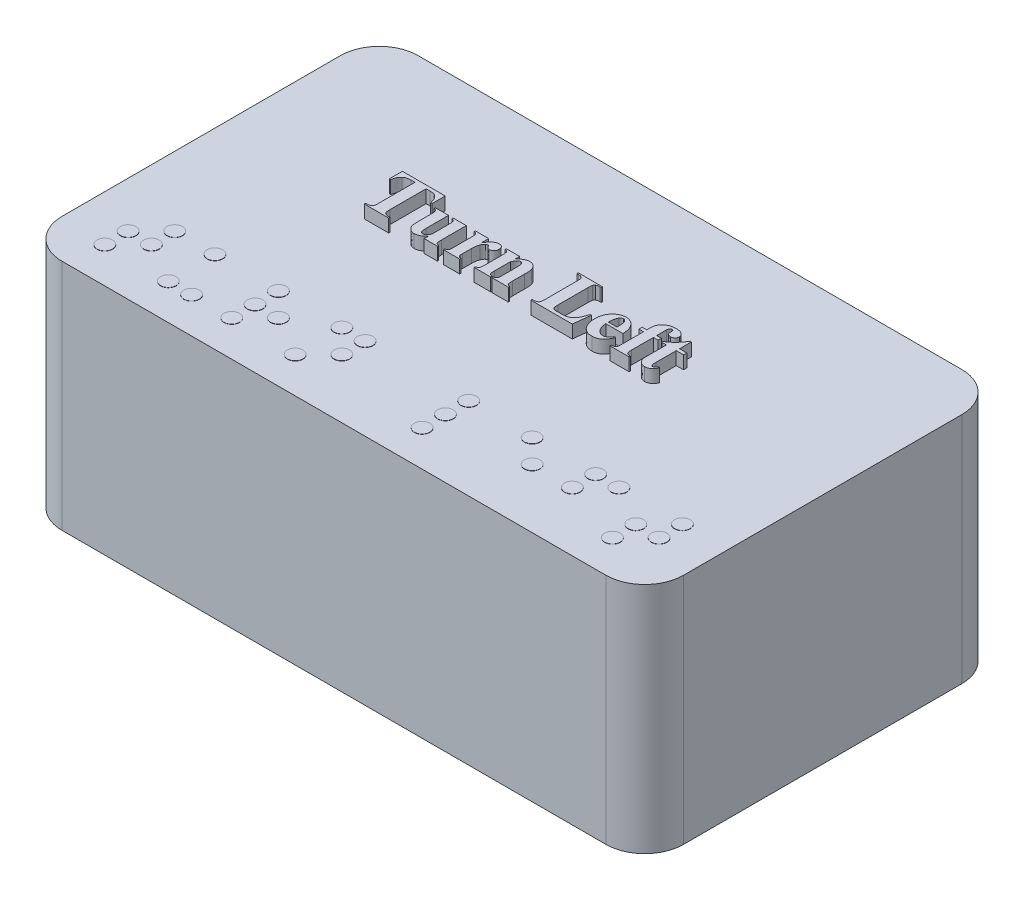
SolidWorks part; units mm, degrees
ref_plane "Front Plane" through (0, 0, 0) normal (0, 0, 1) x (1, 0, 0)
ref_plane "Top Plane" through (0, 0, 0) normal (0, 1, 0) x (1, 0, 0)
ref_plane "Right Plane" through (0, 0, 0) normal (1, 0, 0) x (0, 0, -1)
sketch "Sketch1" plane through (0, 0, 0) normal (0, 1, 0) x (1, 0, 0)
  line L1 (-30.48, 17.4625) -> (30.48, 17.4625)
  line L2 (-30.48, 17.4625) -> (-30.48, -17.4625)
  line L3 (-30.48, -17.4625) -> (30.48, -17.4625)
  line L4 (30.48, 17.4625) -> (30.48, -17.4625)
  line L5 (-30.48, 17.4625) -> (30.48, -17.4625) construction
  line L6 (-30.48, -17.4625) -> (30.48, 17.4625) construction
  point P0 (0, 0)
  dimension "D1" = 60.96
  dimension "D2" = 34.925
extrude "Boss-Extrude1" add sketch "Sketch1" along normal blind 22.86
sketch "Sketch2" plane through (0, 22.86, 0) normal (0, 1, 0) x (1, 0, 0)
  line L0 (-30.48, 17.4625) -> (-30.48, 0.9525) construction
  line L1 (-30.48, 17.4625) -> (-30.48, -17.4625) construction
  line L2 (-30.48, 0.9525) -> (30.48, 0.9525) construction
  line L3 (30.48, -17.4625) -> (30.48, 17.4625) construction
  line L4 (-30.48, 0.9525) -> (-30.48, -9.525) construction
  text T0 "<b>        Turn Left</b>" font "Times New Roman" height in points 19
  dimension "D1" = 16.51
sketch "Sketch3" plane through (0, 22.86, 0) normal (0, 1, 0) x (1, 0, 0)
  line L0 (-30.48, 17.4625) -> (-30.48, 0.9525) construction
  line L1 (-30.48, 17.4625) -> (-30.48, -17.4625) construction
  line L2 (-7.295, -11.6811) -> (-7.295, -13.9671) construction
  line L3 (-25.964, -9.3951) -> (-23.678, -9.3951) construction
  line L4 (-25.964, -9.3951) -> (-25.964, -11.6811) construction
  line L5 (-23.678, -9.3951) -> (-23.678, -11.6811) construction
  line L6 (-25.964, -9.3951) -> (-19.741, -9.3951) construction
  line L7 (-19.741, -9.3951) -> (-17.455, -9.3951) construction
  line L8 (-17.455, -9.3951) -> (-17.455, -11.6811) construction
  line L9 (-19.741, -9.3951) -> (-19.741, -11.6811) construction
  line L10 (-19.741, -11.6811) -> (-19.741, -13.9671) construction
  line L11 (-19.741, -9.3951) -> (-13.518, -9.3951) construction
  line L12 (-13.518, -9.3951) -> (-7.295, -9.3951) construction
  line L13 (-7.295, -9.3951) -> (-7.295, -11.6811) construction
  line L14 (-7.295, -9.3951) -> (-5.009, -9.3951) construction
  line L15 (-7.295, -9.3951) -> (-1.072, -9.3951) construction
  line L16 (-1.072, -9.3951) -> (-1.072, -13.9671) construction
  line L17 (-1.072, -11.6811) -> (1.214, -11.6811) construction
  line L18 (-1.072, -9.3951) -> (5.151, -9.3951) construction
  line L19 (5.151, -9.3951) -> (5.151, -11.6811) construction
  line L20 (5.151, -11.6811) -> (5.151, -13.9671) construction
  line L21 (5.151, -11.6811) -> (7.437, -11.6811) construction
  line L22 (5.151, -9.3951) -> (11.374, -9.3951) construction
  line L23 (11.374, -9.3951) -> (13.66, -9.3951) construction
  line L24 (13.66, -9.3951) -> (13.66, -11.6811) construction
  line L25 (17.597, -9.3951) -> (17.597, -11.6811) construction
  line L26 (17.597, -11.6811) -> (17.597, -13.9671) construction
  line L27 (11.374, -9.3951) -> (17.597, -9.3951) construction
  line L28 (17.597, -9.3951) -> (23.82, -9.3951) construction
  line L29 (23.82, -9.3951) -> (23.82, -11.6811) construction
  line L30 (23.82, -11.6811) -> (23.82, -13.9671) construction
  line L31 (23.82, -11.6811) -> (26.106, -11.6811) construction
  line L32 (23.82, -9.3951) -> (30.043, -9.3951) construction
  line L33 (30.043, -9.3951) -> (32.329, -9.3951) construction
  line L34 (32.329, -9.3951) -> (32.329, -11.6811) construction
  line L35 (-30.48, 0.9525) -> (-30.48, -8.5725) construction
  line L36 (-30.48, -8.5725) -> (30.48, -8.5725) construction
  line L37 (30.48, -17.4625) -> (30.48, 17.4625) construction
  line L38 (-7.295, -11.6811) -> (-5.009, -11.6811) construction
  line L39 (5.151, -13.9671) -> (7.437, -13.9671) construction
  line L40 (17.597, -11.6811) -> (19.883, -11.6811) construction
  line L41 (26.106, -11.6811) -> (26.106, -9.3951) construction
  line L42 (-25.964, -11.6811) -> (-25.964, -13.9671) construction
  line L43 (-19.741, -13.9671) -> (-17.455, -13.9671) construction
  line L44 (-13.518, -9.3951) -> (-13.518, -11.6811) construction
  line L45 (-13.518, -11.6811) -> (-13.518, -13.9671) construction
  line L46 (-13.518, -11.6811) -> (-11.232, -11.6811) construction
  line L47 (13.66, -11.6811) -> (11.374, -11.6811) construction
  line L48 (17.597, -9.3951) -> (19.883, -9.3951) construction
  line L49 (32.329, -11.6811) -> (30.043, -11.6811) construction
  line L50 (30.043, -11.6811) -> (30.043, -13.9671) construction
  circle A1 centre (-25.964, -11.6811) radius 0.762
  circle A2 centre (-23.678, -9.3951) radius 0.762
  circle A3 centre (-23.678, -11.6811) radius 0.762
  circle A9 centre (-19.741, -9.3951) radius 0.762
  circle A11 centre (-19.741, -13.9671) radius 0.762
  circle A12 centre (-7.295, -9.3951) radius 0.762
  circle A18 centre (5.151, -9.3951) radius 0.762
  circle A19 centre (5.151, -11.6811) radius 0.762
  circle A20 centre (5.151, -13.9671) radius 0.762
  circle A26 centre (17.597, -9.3951) radius 0.762
  circle A29 centre (23.82, -11.6811) radius 0.762
  circle A34 centre (-7.295, -13.9671) radius 0.762
  circle A35 centre (-5.009, -11.6811) radius 0.762
  circle A39 centre (17.597, -11.6811) radius 0.762
  circle A43 centre (-25.964, -13.9671) radius 0.762
  circle A44 centre (-17.455, -13.9671) radius 0.762
  circle A45 centre (-13.518, -9.3951) radius 0.762
  circle A46 centre (-13.518, -11.6811) radius 0.762
  circle A47 centre (-13.518, -13.9671) radius 0.762
  circle A48 centre (-11.232, -11.6811) radius 0.762
  circle A49 centre (-5.009, -9.3951) radius 0.762
  circle A53 centre (19.883, -9.3951) radius 0.762
  circle A55 centre (26.106, -11.6811) radius 0.762
  circle A59 centre (11.374, -9.3951) radius 0.762
  circle A60 centre (13.66, -11.6811) radius 0.762
  circle A61 centre (23.82, -13.9671) radius 0.762
  circle A62 centre (26.106, -9.3951) radius 0.762
  dimension "D9" = 6.223
  dimension "D10" = 6.223
  dimension "D11" = 2.286
  dimension "D12" = 6.223
  dimension "D13" = 2.286
  dimension "D15" = 2.286
  dimension "D16" = 6.223
  dimension "D20" = 6.223
  dimension "D21" = 6.223
  dimension "D22" = 2.286
  dimension "D25" = 6.223
  dimension "D26" = 2.286
  dimension "D28" = 16.51
  dimension "D31" = 2.286
  dimension "D32" = 2.286
  dimension "D33" = 2.286
  dimension "D19" = 2.286
  dimension "D34" = 2.286
  dimension "D35" = 2.286
  dimension "D38" = 2.286
  dimension "D1" = 2.286
  dimension "D2" = 2.286
  dimension "D3" = 2.286
  dimension "D4" = 6.223
  dimension "D5" = 2.286
  dimension "D6" = 2.286
  dimension "D7" = 2.286
  dimension "D8" = 6.223
  dimension "D14" = 2.286
  dimension "D17" = 2.286
  dimension "D18" = 2.286
  dimension "D23" = 2.286
  dimension "D24" = 2.286
  dimension "D27" = 2.286
  dimension "D29" = 9.525
  dimension "D30" = 2.286
  dimension "D36" = 2.286
  dimension "D37" = 2.286
extrude "Boss-Extrude3" add sketch "Sketch2" along normal blind 1.27
extrude "Boss-Extrude4" add sketch "Sketch3" along normal blind 0.0254
sketch "Sketch6" plane through (0, 0, 0) normal (0, -1, 0) x (-1, 0, 0)
  line L0 (30.48, -17.4625) -> (30.48, 0) construction
  line L1 (30.48, 17.4625) -> (30.48, -17.4625) construction
  line L2 (30.48, 0) -> (25.4, 0) construction
  line L3 (-30.48, -17.4625) -> (-30.48, 0) construction
  line L4 (-30.48, -17.4625) -> (-30.48, 17.4625) construction
  line L5 (-30.48, 0) -> (-25.4, 0) construction
  circle A0 centre (25.4, 0) radius 3.15
  circle A1 centre (-25.4, 0) radius 3.15
  dimension "D1" = 5.08
  dimension "D2" = 5.08
extrude "Cut-Extrude1" cut sketch "Sketch6" against normal blind 3.25
sketch "Sketch7" plane through (0, 0, 0) normal (0, -1, 0) x (-1, 0, 0)
  line L1 (20.828, -11.43) -> (-20.828, -11.43)
  line L2 (20.828, -11.43) -> (20.828, 11.43)
  line L3 (20.828, 11.43) -> (-20.828, 11.43)
  line L4 (-20.828, -11.43) -> (-20.828, 11.43)
  line L5 (20.828, -11.43) -> (-20.828, 11.43) construction
  line L6 (20.828, 11.43) -> (-20.828, -11.43) construction
  point P0 (0, 0)
  dimension "D1" = 41.656
  dimension "D2" = 22.86
extrude "Cut-Extrude2" cut sketch "Sketch7" against normal blind 17.78
fillet "Fillet2" radius 3.81 4 edges at (-30.48, 11.43, -17.4625) (30.48, 11.43, -17.4625) (30.48, 11.43, 17.4625) (-30.48, 11.43, 17.4625)
sketch "Sketch8" plane through (0, 17.78, 0) normal (0, -1, 0) x (1, 0, 0)
  line L1 (-20.828, 11.43) -> (-12.7, 11.43)
  line L2 (-20.828, 11.43) -> (-20.828, 3.302)
  line L3 (-20.828, 3.302) -> (-12.7, 3.302)
  line L4 (-12.7, 11.43) -> (-12.7, 3.302)
  line L5 (20.828, -11.43) -> (12.7, -11.43)
  line L6 (20.828, -11.43) -> (20.828, -3.302)
  line L7 (20.828, -3.302) -> (12.7, -3.302)
  line L8 (12.7, -11.43) -> (12.7, -3.302)
  dimension "D1" = 8.128
  dimension "D2" = 8.128
  dimension "D3" = 8.128
  dimension "D4" = 8.128
extrude "Boss-Extrude5" add sketch "Sketch8" along normal blind 13.97
